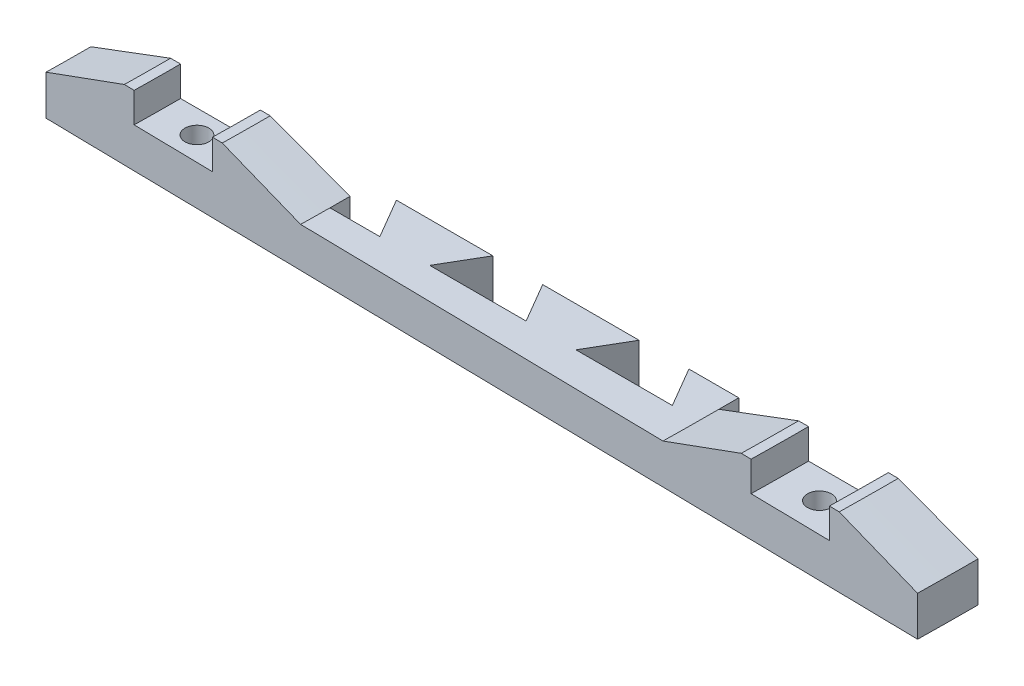
SolidWorks part; units mm, degrees
other "标注1"
sketch "草图3" plane through (-22.25, 4, -10) normal (-0.231, 0.6469, -0.7268) x (-0.9696, -0.2151, 0.1167)
ref_plane "前视基准面" through (0, 0, 0) normal (0, 0, 1) x (1, 0, 0)
ref_plane "上视基准面" through (0, 0, 0) normal (0, 1, 0) x (1, 0, 0)
ref_plane "右视基准面" through (0, 0, 0) normal (1, 0, 0) x (0, 0, -1)
other "Configuration Table"
sketch "草图4" plane through (0, 0, 0) normal (0, 0, 1) x (1, 0, 0)
  line L6 (8.5, -1.5) -> (17.75, -1.5)
  line L11 (17.75, -1.5) -> (17.75, -3.5)
  line L16 (17.75, -3.5) -> (-4.5, -3.5)
  line L17 (-4.5, -3.5) -> (-4.5, -1.5)
  line L19 (0, 0) -> (0, -1.5)
  line L20 (0, -1.5) -> (4, -1.5)
  line L21 (4, -1.5) -> (4, 0)
  line L26 (4, 0) -> (4.5, 0)
  line L27 (4.5, 0) -> (8.5, -1.5)
  line L28 (0, 0) -> (-0.5, 0)
  line L29 (-0.5, 0) -> (-4.5, -1.5)
  dimension "D2" = 4
  dimension "D4" = 0.5
  dimension "D5" = 2
  dimension "D6" = 2
  dimension "D7" = 4
  dimension "D8" = 1.5
  dimension "D9" = 4
  dimension "D10" = 22.25
extrude "凸台-拉伸1" add sketch "草图4" along normal blind 2.5 contours L28 L29 L17 L16 L11 L6 L27 L26 L21 L20 L19 | L19 | L21 region at (5.9579, -2.2764, 0)
sketch "草图5" plane through (0, -1.5, 0) normal (0, 1, 0) x (1, 0, 0)
  line L0 (0, 0) -> (4, -2.5) construction
  line L1 (0, -2.5) -> (0, 0) construction
  line L2 (0, -2.5) -> (4, -2.5) construction
  line L3 (4, -2.5) -> (4, 0) construction
  line L4 (0, 0) -> (4, 0) construction
  circle A0 centre (2, -1.25) radius 0.6
  circle A1 centre (2, -1.25) radius 1
  dimension "D1" = 1.2
  dimension "D2" = 2
extrude "切除-拉伸1" cut sketch "草图5" against normal through all contours A0
extrude "切除-拉伸2" cut sketch "草图5<3>" along normal blind 1 from surface contours A1 starting at face at (2, -3.5, 1.85)
sketch "草图5<3>" plane through (0, -1.5, 0) normal (0, 1, 0) x (1, 0, 0) same geometry as "草图5"
mirror "镜向1" about plane through (17.75, 0, 2.5) normal (1, 0, 0) of bodies 215
sketch "草图6" plane through (0, 0, 2.5) normal (0, 0, 1) x (1, 0, 0)
  line L18 (0, 0) -> (-0.5, 0)
  line L19 (-0.5, 0) -> (-4.5, -1.5)
  line L20 (-4.5, -1.5) -> (-4.5, -3.5)
  line L21 (-4.5, -3.5) -> (40, -3.5)
  line L22 (40, -3.5) -> (40, -1.5)
  line L23 (40, -1.5) -> (36, 0)
  line L24 (36, 0) -> (35.5, 0)
  line L25 (35.5, 0) -> (35.5, -1.5)
  line L26 (35.5, -1.5) -> (31.5, -1.5)
  line L27 (31.5, -1.5) -> (31.5, 0)
  line L28 (31.5, 0) -> (31, 0)
  line L29 (31, 0) -> (27, -1.5)
  line L30 (27, -1.5) -> (8.5, -1.5)
  line L31 (8.5, -1.5) -> (4.5, 0)
  line L32 (4.5, 0) -> (4, 0)
  line L33 (4, 0) -> (4, -1.5)
  line L34 (4, -1.5) -> (0, -1.5)
  line L35 (0, -1.5) -> (0, 0)
  line L36 (0, 0) -> (-0.5, 0)
  line L37 (-0.5, 0) -> (-4.5, -1.5)
  line L38 (-4.5, -1.5) -> (-4.5, -3.5)
  line L39 (-4.5, -3.5) -> (40, -3.5)
  line L40 (40, -3.5) -> (40, -1.5)
  line L41 (40, -1.5) -> (36, 0)
  line L42 (36, 0) -> (35.5, 0)
  line L43 (35.5, 0) -> (35.5, -1.5)
  line L44 (35.5, -1.5) -> (31.5, -1.5)
  line L45 (31.5, -1.5) -> (31.5, 0)
  line L46 (31.5, 0) -> (31, 0)
  line L47 (31, 0) -> (27, -1.5)
  line L48 (27, -1.5) -> (8.5, -1.5)
  line L49 (8.5, -1.5) -> (4.5, 0)
  line L50 (4.5, 0) -> (4, 0)
  line L51 (4, 0) -> (4, -1.5)
  line L52 (4, -1.5) -> (0, -1.5)
  line L53 (0, -1.5) -> (0, 0)
  dimension "D1" = 0
sketch "草图8" plane through (0, 0, 2.5) normal (0, 0, 1) x (1, 0, 0)
  line L0 (-132.25, 94.8536) -> (-132.25, -34.2886)
  line L1 (17.75, -1.5) -> (17.75, -3.5)
  line L2 (27, -1.5) -> (8.5, -1.5) construction
  line L3 (-4.5, -3.5) -> (40, -3.5) construction
  dimension "D1" = 150
revolve "旋转1" add sketch "草图6" angle 1 about L0
sketch "草图9" plane through (0, -1.5, 0) normal (0, 1, 0) x (1, 0, 0)
  line L0 (-0.005, -3.6541) -> (3.9948, -3.689) construction
  line L1 (3.9948, -3.689) -> (31.4938, -3.929) construction
  line L2 (31.4938, -3.929) -> (35.4936, -3.9639) construction
  arc A0 (-0.0201, -4.8081) -> (0, -2.5) centre (-132.25, -2.5) ccw construction
  arc A1 (3.9792, -4.8779) -> (4, -2.5) centre (-132.25, -2.5) ccw construction
  arc A2 (31.4751, -5.3578) -> (31.5, -2.5) centre (-132.25, -2.5) ccw construction
  arc A3 (35.4745, -5.4276) -> (35.5, -2.5) centre (-132.25, -2.5) ccw construction
  circle A4 centre (1.9949, -3.6715) radius 1
  circle A5 centre (1.9949, -3.6715) radius 0.6
  circle A6 centre (33.4937, -3.9464) radius 1
  circle A7 centre (33.4937, -3.9464) radius 0.6
  dimension "D1" = 2
  dimension "D2" = 1.2
extrude "切除-拉伸3" cut sketch "草图9" against normal through all contours A7 | A5
extrude "切除-拉伸4" cut sketch "草图9<3>" along normal blind 1 from surface contours A6 | A4 starting at face at (32.8937, -3.5, 3.9464)
sketch "草图9<3>" plane through (0, -1.5, 0) normal (0, 1, 0) x (1, 0, 0) same geometry as "草图9"
sketch "草图10" plane through (0, -1.5, 0) normal (0, 1, 0) x (1, 0, 0)
  line L0 (27, -2.5) -> (27, -1.5)
  line L1 (27, -2.5) -> (27, 0) construction
  line L2 (27, -1.5) -> (24.5, -1.5)
  line L3 (24.5, -1.5) -> (25.6679, -3.5)
  line L4 (25.6679, -3.5) -> (20.8321, -3.5)
  line L5 (20.8321, -3.5) -> (22, -1.5)
  line L6 (22, -1.5) -> (17.1643, -1.5)
  line L7 (17.1643, -1.5) -> (18.3321, -3.5)
  line L8 (18.3321, -3.5) -> (13.4964, -3.5)
  line L9 (13.4964, -3.5) -> (14.6643, -1.5)
  line L10 (14.6643, -1.5) -> (9.8286, -1.5)
  line L11 (9.8286, -1.5) -> (10.9964, -3.5)
  line L12 (10.9964, -3.5) -> (8.4964, -3.5)
  line L13 (8.5, -2.5) -> (8.4964, -3.5)
  line L14 (24.5, -1.5) -> (22, -1.5) construction
  line L15 (17.1643, -1.5) -> (14.6643, -1.5) construction
  line L16 (20.8321, -3.5) -> (18.3321, -3.5) construction
  line L17 (13.4964, -3.5) -> (10.9964, -3.5) construction
  line L18 (23.25, -3.5) -> (23.25, -1.5) construction
  line L19 (27, -2.5) -> (23.25, -2.5) construction
  line L20 (27, -2.5) -> (40, -2.5)
  line L21 (8.5, -2.5) -> (-4.5, -2.5)
  line L22 (-4.5, -2.5) -> (-4.5, 0)
  line L23 (-4.5, 0) -> (40, 0)
  line L24 (40, 0) -> (40, -2.5)
  arc A0 (8.4786, -4.9564) -> (8.5, -2.5) centre (-132.25, -2.5) ccw construction
  point P23 (40, -5.85)
  point P33 (40.8248, -5.7017)
  point P34 (-4.5, 0)
  point P36 (40, 0)
  dimension "D1" = 2.5
  dimension "D2" = 2
extrude "切除-拉伸9" cut sketch "草图10" against normal through all both and the other way through all
